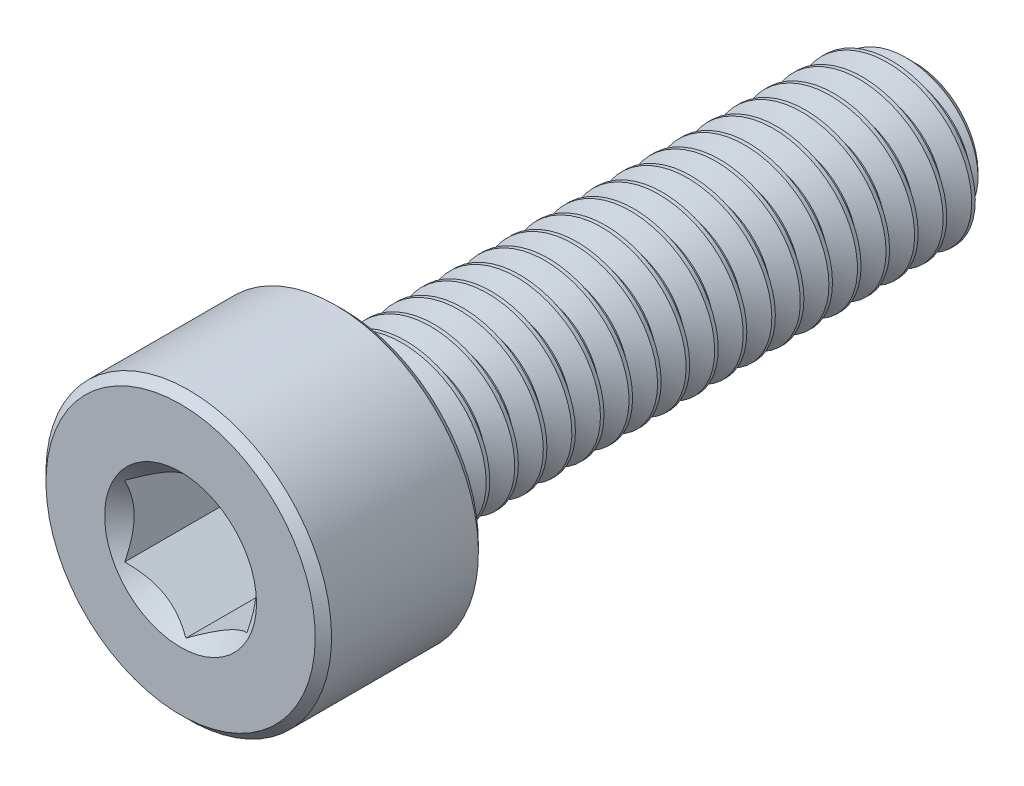
SolidWorks part; units mm, degrees
ref_plane "Front Plane" through (0, 0, 0) normal (0, 0, 1) x (1, 0, 0)
ref_plane "Top Plane" through (0, 0, 0) normal (0, 1, 0) x (1, 0, 0)
ref_plane "Right Plane" through (0, 0, 0) normal (1, 0, 0) x (0, 0, -1)
sketch "Sketch1" plane through (0, 0, 0) normal (1, 0, 0) x (0, 0, -1)
  line L0 (-9, 0) -> (9, 0) construction
  line L1 (9, 0) -> (9, 1.5453) construction
  line L2 (9, 1.5453) -> (8.5453, 2) construction
  line L3 (8.5453, 2) -> (8.475, 2) construction
  line L4 (8.475, 2) -> (-5, 2) construction
  line L5 (-5, 2) -> (-5, 3.5) construction
  line L6 (-5, 3.5) -> (-9, 3.5) construction
  line L7 (-9, 3.5) -> (-9, 0) construction
  line L8 (9, 1.5453) -> (9, 2) construction
  line L9 (8.9563, 2.0758) -> (9.3063, 1.4696) construction
  line L10 (9.3063, 1.4696) -> (9.6563, 2.0758) construction
  line L11 (9.6563, 2.0758) -> (8.9563, 2.0758) construction
  line L12 (9.3063, 2.0758) -> (9.3063, 2) construction
  line L13 (9.3063, 1.4696) -> (9.3063, 1.5453) construction
  line L14 (9.2625, 1.5453) -> (9.35, 1.5453) construction
  line L15 (9, 2) -> (9.6125, 2) construction
  line L16 (8.9781, 2.0379) -> (9.6344, 2.0379) construction
  line L17 (9, 0) -> (9, -2) construction
  line L18 (-5.2, 3.5) -> (-5, 3.3) construction
  line L19 (-8.8, 3.5) -> (-9, 3.3) construction
  line L20 (-5, 2) -> (-5, 0) construction
  line L21 (-5, 1) -> (-0.3333, 1) construction
  line L22 (-0.3333, 1) -> (4.3333, 1) construction
  line L23 (4.3333, 1) -> (9, 1) construction
  line L24 (-0.3333, 1) -> (-0.3333, 2) construction
  line L25 (-0.3333, 2) -> (-0.3333, 3.5) construction
  line L26 (4.3333, 1) -> (4.3333, 3.5) construction
  point P0 (-9, 1.5)
  point P3 (7.25, 2)
  point P4 (0, 0)
  point P18 (4.3333, 2)
  point P22 (9.3063, 1.5453)
  point P24 (8.475, 2)
  point P25 (9.3063, 2)
  point P28 (9.3063, 2.0379)
  point P29 (7.25, -2)
  point P30 (-0.3333, 2)
  point P31 (-7, 3.5)
  point P37 (-5.7, 3.5)
  point P38 (-8.7, 3.5)
  point P45 (-0.3333, 1)
  point P46 (4.3333, 1)
  dimension "D2" = 0.0875
  dimension "D7" = 0.2
  dimension "D8" = 0.2
  dimension "D9" = 0.2
  dimension "D10" = 0.1
  dimension "D11" = 0.5
  dimension "Drive Size" = 3
  dimension "Head Diameter" = 7
  dimension "Head Height" = 4
  dimension "Thread Pitch" = 0.7
  dimension "Thread Size" = 4
  dimension "Length" = 14
  dimension "D12" = 0.525
  dimension "D4" = 1.75
  dimension "D3" = 45
sketch "Sketch2" plane through (0, 0, 0) normal (1, 0, 0) x (0, 0, -1)
  line L0 (-9, 0) -> (-9, 3.3)
  line L1 (-8.8, 3.5) -> (-5.2, 3.5)
  line L2 (-5, 3.3) -> (-5, 2.2)
  line L4 (8.5453, 2) -> (9, 1.5453)
  line L5 (9, 1.5453) -> (9, 0)
  line L6 (-5, 3.5) -> (-9, 3.5) construction
  line L7 (9, 0) -> (-9, 0)
  line L8 (-8.8, 3.5) -> (-9, 3.3) construction
  line L10 (-8.8, 3.5) -> (-9, 3.3)
  line L14 (-5.2, 3.5) -> (-5, 3.3) construction
  line L16 (-5.2, 3.5) -> (-5, 3.3)
  line L17 (-5, 2) -> (-5, 3.5) construction
  line L19 (-4.8, 2) -> (8.5453, 2)
  line L20 (8.475, 2) -> (-5, 2) construction
  arc A1 (-5, 2.2) -> (-4.8, 2) centre (-4.8, 2.2) ccw
  dimension "D3" = 0.2
revolve "Revolve1" add sketch "Sketch2" angle 360 about L7
sketch "Sketch3" plane through (0, 0, 9) normal (0, 0, 1) x (1, 0, 0)
  line L1 (1.5, -0.866) -> (1.5, 0.866)
  line L2 (1.5, 0.866) -> (0, 1.7321)
  line L3 (0, 1.7321) -> (-1.5, 0.866)
  line L4 (-1.5, 0.866) -> (-1.5, -0.866)
  line L5 (-1.5, -0.866) -> (0, -1.7321)
  line L6 (0, -1.7321) -> (1.5, -0.866)
  circle A0 centre (0, 0) radius 1.5 construction
  circle A1 centre (0, 0) radius 3.5 construction
  circle A2 centre (0, 0) radius 3.5 construction
  circle A3 centre (0, 0) radius 1.7321 construction
  point P13 (0, 0)
  dimension "D1" = 3.4641
extrude "Cut-Extrude1" cut sketch "Sketch3" against normal offset from surface (3 mm away) 1 up to face at (0, 3.3, 5)
sketch "Sketch4" plane through (0, 0, 9) normal (0, 0, 1) x (1, 0, 0)
  circle A0 centre (0, 0) radius 1.862
  dimension "D1" = 3.7239
extrude "Cut-Extrude2" cut sketch "Sketch4" against normal up to vertex (2 mm away) draft 45 up to point (0, 3.5, 7)
sketch "Sketch11" plane through (0, 0, 0) normal (1, 0, 0) x (0, 0, -1)
  line L0 (-9, 0) -> (9, 0) construction
  line L1 (-9, 0) -> (9, 0) construction
  line L2 (-2.375, 0) -> (-2.375, 2) construction
  line L3 (8.475, 2) -> (-5, 2) construction
  line L4 (6.375, 0) -> (6.375, 2) construction
  line L6 (9, 1.5453) -> (9, 2) construction
  point P2 (-2.375, 0)
  point P3 (6.375, 0)
  dimension "D1" = 2.625
  dimension "D2" = 2.625
sketch "Sketch6" plane through (0, 0, -9) normal (0, 0, -1) x (-1, 0, 0)
  circle A0 centre (0, 0) radius 2
curve "Helix/Spiral1" pitch 0.7 height 14.7 radius 2 centre (0, 0, -9) axis (0, 0, 1) start towards (0, 1, 0)
sketch "Sketch10" plane through (0, 0, 0) normal (1, 0, 0) x (0, 0, -1)
  line L0 (-4.8, -3.5) -> (-4.8, 3.5)
  line L5 (-9, 0) -> (9, 0) construction
  line L6 (-4.8, 2) -> (-4.8, -2) construction
  point P3 (-4.8, 0)
split "Split1" trim tools "Sketch10" bodies to split 106 resulting bodies 114 115
sketch "Sketch7" plane through (0, 0, 0) normal (1, 0, 0) x (0, 0, -1)
  line L0 (8.9781, 2.0379) -> (9.6344, 2.0379)
  line L1 (9.6344, 2.0379) -> (9.35, 1.5453)
  line L2 (9.35, 1.5453) -> (9.2625, 1.5453)
  line L3 (9.2625, 1.5453) -> (8.9781, 2.0379)
sweep "Cut-Sweep1" cut profiles "Sketch7" path "Helix/Spiral1" align with end faces yes
sketch "Sketch8" plane through (0, 0, 0) normal (1, 0, 0) x (0, 0, -1)
  line L0 (-5, 0) -> (-5, 2)
  line L1 (-4.8, -2) -> (-4.8, 2) construction
  line L2 (-5, 2) -> (-4.8, 2)
  line L4 (-4.8, 2) -> (-3.6453, 0)
  line L5 (-3.6453, 0) -> (-5, 0)
  line L6 (8.475, 2) -> (-5, 2) construction
  line L7 (-9, 0) -> (9, 0) construction
  dimension "D1" = 60
revolve "Revolve2" add sketch "Sketch8" angle 360 about L5
equation "\"D2@Sketch1\" = \"Thread Pitch@Sketch1\" / 8"
equation "\"D4@Helix/Spiral1\" = \"Thread Pitch@Sketch1\""
equation "\"D7@Sketch1\" = \"Head Height@Sketch1\" * .05"
equation "\"D8@Sketch1\"=\"D7@Sketch1\""
equation "\"D9@Sketch1\"=\"D7@Sketch1\""
equation "\"D10@Sketch1\"=\"D7@Sketch1\"/2"
equation "\"D11@Sketch1\"=\"D10@Sketch1\"*5"
equation "\"D4@Sketch1\"=\"Thread Pitch@Sketch1\"*2.5"
equation "\"D12@Sketch1\"=\"Thread Pitch@Sketch1\"*.75"
equation "\"D3@Helix/Spiral1\"=\"Length@Sketch1\"+\"Thread Pitch@Sketch1\""
equation "\"D3@Sketch2\"=\"Thread Size@Sketch1\"*0.05"
equation "\"D1@Sketch11\"=\"Length@Sketch1\"*0.1875"
equation "\"D2@Sketch11\"=\"D1@Sketch11\""
equation "\"D1@Sketch4\"=\"D1@Sketch3\"*1.075"
